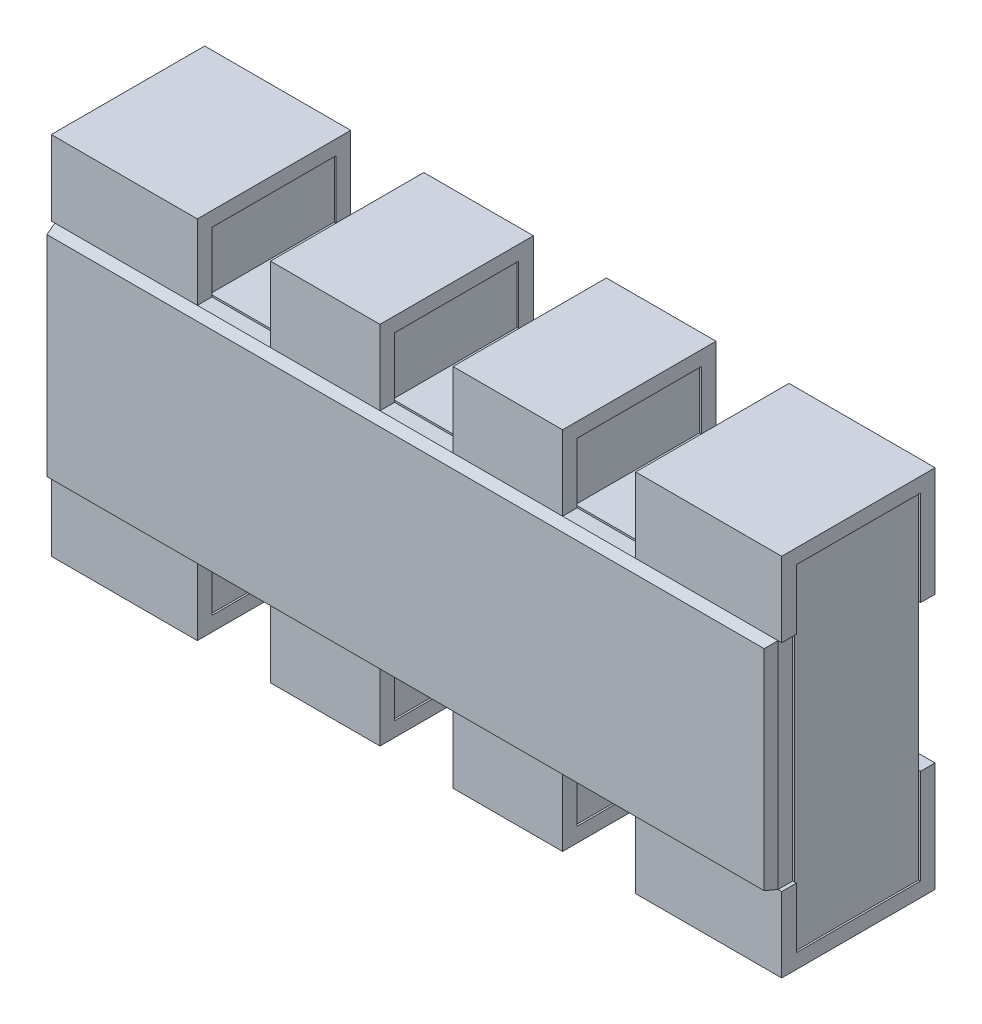
SolidWorks part; units mm, degrees
ref_plane "Спереди" through (0, 0, 0) normal (0, 0, 1) x (1, 0, 0)
ref_plane "Сверху" through (0, 0, 0) normal (0, 1, 0) x (1, 0, 0)
ref_plane "Справа" through (0, 0, 0) normal (1, 0, 0) x (0, 0, -1)
sketch "Эскиз1" plane through (0, 0, 0) normal (0, 0, 1) x (1, 0, 0)
  line L0 (-0.605, 0.49) -> (-0.605, 0.3)
  line L1 (0.605, 0.49) -> (0.995, 0.49)
  line L2 (-0.395, -0.3) -> (-0.605, -0.3)
  line L3 (0.605, -0.49) -> (0.995, -0.49)
  line L4 (0.995, 0.49) -> (0.995, -0.49)
  line L5 (-0.995, 0.49) -> (-0.605, 0.49)
  line L6 (-0.995, 0.49) -> (-0.995, -0.49)
  line L7 (-0.995, -0.49) -> (-0.605, -0.49)
  line L9 (0.105, 0.49) -> (0.395, 0.49)
  line L11 (0.105, -0.49) -> (0.395, -0.49)
  line L13 (-0.105, 0.49) -> (-0.395, 0.49)
  line L15 (-0.105, -0.49) -> (-0.395, -0.49)
  line L18 (-0.105, 0.49) -> (-0.105, 0.3)
  line L20 (-0.395, 0.49) -> (-0.395, 0.3)
  line L22 (-0.395, 0.3) -> (-0.605, 0.3)
  line L26 (0.105, 0.49) -> (0.105, 0.3)
  line L28 (0.105, 0.3) -> (-0.105, 0.3)
  line L30 (0.395, 0.49) -> (0.395, 0.3)
  line L32 (0.395, 0.3) -> (0.605, 0.3)
  line L35 (0.605, 0.3) -> (0.605, 0.49)
  line L40 (-0.605, -0.49) -> (-0.605, -0.3)
  line L48 (-0.395, -0.3) -> (-0.395, -0.49)
  line L49 (-0.105, -0.49) -> (-0.105, -0.3)
  line L50 (-0.105, -0.3) -> (0.105, -0.3)
  line L51 (0.105, -0.3) -> (0.105, -0.49)
  line L52 (0.395, -0.49) -> (0.395, -0.3)
  line L53 (0.395, -0.3) -> (0.605, -0.3)
  line L60 (0.605, -0.3) -> (0.605, -0.49)
extrude "Вытянуть1" add sketch "Эскиз1" along normal blind 0.34 from offset 0.04
sketch "Эскиз2" plane through (0, 0, 0) normal (0, 0, 1) x (1, 0, 0)
  line L1 (-0.99, 0.295) -> (0.99, 0.295)
  line L2 (-0.99, 0.295) -> (-0.99, -0.295)
  line L3 (-0.99, -0.295) -> (0.99, -0.295)
  line L4 (0.99, 0.295) -> (0.99, -0.295)
extrude "Бобышка-Вытянуть1" add sketch "Эскиз2" along normal blind 0.03 draft 15 and the other way blind 0.04 from offset 0.42
sketch "Эскиз3" plane through (0, 0, 0) normal (1, 0, 0) x (0, 0, -1)
  line L0 (-0.42, 0.295) -> (-0.38, 0.295)
  line L1 (-0.42, 0.5) -> (0, 0.5)
  line L2 (-0.42, 0.5) -> (-0.42, 0.295)
  line L4 (0, 0.5) -> (0, 0.2)
  line L5 (-0.38, 0.295) -> (-0.38, 0.46)
  line L6 (-0.38, 0.46) -> (-0.04, 0.46)
  line L7 (-0.04, 0.46) -> (-0.04, 0.2)
  line L9 (-0.04, 0.2) -> (0, 0.2)
  line L10 (0, 0) -> (-0.5306, 0) construction
  line L11 (-0.04, -0.2) -> (0, -0.2)
  line L12 (-0.04, -0.46) -> (-0.04, -0.2)
  line L13 (-0.38, -0.46) -> (-0.04, -0.46)
  line L14 (-0.38, -0.295) -> (-0.38, -0.46)
  line L15 (0, -0.5) -> (0, -0.2)
  line L16 (-0.42, -0.5) -> (-0.42, -0.295)
  line L17 (-0.42, -0.5) -> (0, -0.5)
  line L18 (-0.42, -0.295) -> (-0.38, -0.295)
extrude "Бобышка-Вытянуть3" add sketch "Эскиз3" along normal blind 0.3 from offset 0.4 offset against normal yes
extrude "Бобышка-Вытянуть4" add sketch "Эскиз3<2>" along normal blind 0.4 from offset 1 offset against normal yes
sketch "Эскиз3<2>" plane through (0, 0, 0) normal (1, 0, 0) x (0, 0, -1) same geometry as "Эскиз3"
extrude "Бобышка-Вытянуть5" add sketch "Эскиз3<3>" against normal blind 0.4 from offset 1
sketch "Эскиз3<3>" plane through (0, 0, 0) normal (1, 0, 0) x (0, 0, -1) same geometry as "Эскиз3"
pattern_linear "Линейный массив1" count 2 spacing 0.5 along (1, 0, 0) of "Бобышка-Вытянуть3"
